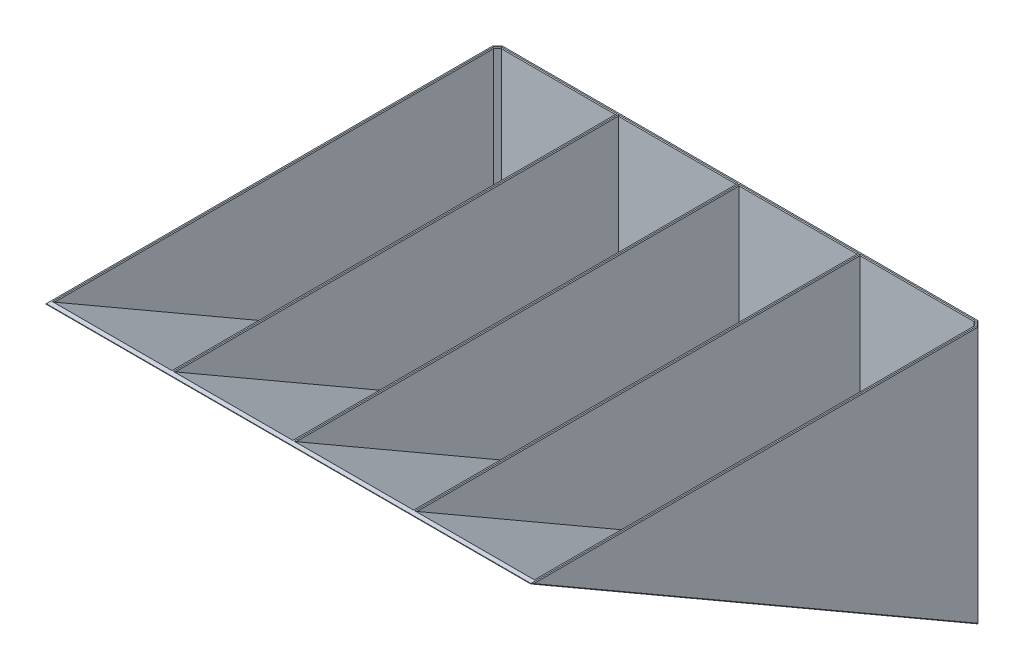
SolidWorks part; units mm, degrees
ref_plane "Front" through (0, 0, 0) normal (0, 0, 1) x (1, 0, 0)
ref_plane "Top" through (0, 0, 0) normal (0, 1, 0) x (1, 0, 0)
ref_plane "Right" through (0, 0, 0) normal (1, 0, 0) x (0, 0, -1)
sketch "Sketch1" plane through (0, 0, 0) normal (1, 0, 0) x (0, 0, -1)
  line L0 (0, 139.892) -> (0, 0)
  line L1 (0, 0) -> (-242.3, 139.892)
  line L2 (-242.3, 139.892) -> (0, 139.892)
  dimension "D1" = 60
extrude "Boss-Extrude1" add sketch "Sketch1" along normal up to surface (130.1 mm away) and the other way up to surface (130.1 mm away)
chamfer "Back Corner Chams" distance 3 angle 45 2 edges at (130.1, 69.946, 0) (-130.1, 69.946, 0)
shell "Compartment" thickness 1.5
sketch "Sketch7" plane through (0, 0, 0) normal (1, 0, 0) x (0, 0, -1)
  line L0 (-233.5531, 134.842) -> (-229.0426, 129.4665)
  line L1 (0, 0) -> (-242.3, 139.892) construction
  line L2 (-229.0426, 129.4665) -> (-226.5135, 128.0063)
  line L3 (-226.5135, 128.0063) -> (-224.1135, 129.392)
  line L4 (-233.5531, 134.842) -> (-224.1135, 129.392)
  dimension "D1" = 60
  dimension "D2" = 2.4
  dimension "D3" = 10.1
  dimension "D4" = 20
  dimension "D5" = 10.9
extrude "Stacker Rib" add sketch "Sketch7" along normal offset from surface 10.1 and the other way offset from surface (120 mm away) 10.1 up to face at (130.1, 93.8387, 82.7667) other way up to face at (-130.1, 93.8387, 82.7667)
chamfer "Stacker Rib Cham" distance 2.4 angle 45 2 edges at (120, 128.7364, 227.778) (-120, 128.7364, 227.778)
pattern_linear "LPattern1" count 8 spacing 35 along (0, -0.5, -0.866) of "Stacker Rib", "Stacker Rib Cham"
sketch "Sketch3" plane through (0, 0, 0) normal (1, 0, 0) x (0, 0, -1)
  line L3 (0, 0) -> (0, 139.892)
  line L4 (-242.3, 139.892) -> (0, 0)
  line L5 (0, 139.892) -> (-242.3, 139.892)
  line L6 (0, 0) -> (0, 139.892)
  line L7 (-242.3, 139.892) -> (0, 0)
  line L8 (0, 139.892) -> (-242.3, 139.892)
  dimension "D1" = 0
extrude "Center Divider" add sketch "Sketch3" along normal mid plane 1.5
sketch "Sketch4" [suppressed] plane through (0, 139.892, 0) normal (0, 1, 0) x (1, 0, 0)
  line L0 (-128.6, -121.4607) -> (-42.8667, -121.4607) construction
  line L1 (-128.6, -239.3) -> (-128.6, -3.6213) construction
  line L2 (-42.8667, -121.4607) -> (42.8667, -121.4607) construction
  line L3 (42.8667, -121.4607) -> (128.6, -121.4607) construction
  line L4 (128.6, -3.6213) -> (128.6, -239.3) construction
ref_plane "3 Compartment Divider Plane" [suppressed] through (-42.8667, 0, 0) normal (1, 0, 0) x (0, 0, -1)
sketch "Sketch5" [suppressed] plane through (-42.8667, 0, 0) normal (1, 0, 0) x (0, 0, -1)
  line L3 (0, 0) -> (0, 139.892)
  line L4 (0, 139.892) -> (-242.3, 139.892)
  line L5 (-242.3, 139.892) -> (0, 0)
  line L6 (0, 0) -> (0, 139.892)
  line L7 (0, 139.892) -> (-242.3, 139.892)
  line L8 (-242.3, 139.892) -> (0, 0)
  dimension "D1" = 0
extrude "3 Divider Left" [suppressed] add sketch "Sketch5" along normal mid plane 1.5
mirror "3 Divider Right" [suppressed] about plane through (0, 0, 0) normal (1, 0, 0)
ref_plane "4 Compartment Divider Plane" through (-64.675, 0, 0) normal (1, 0, 0) x (0, 0, -1)
sketch "Sketch6" plane through (-64.675, 0, 0) normal (1, 0, 0) x (0, 0, -1)
  line L3 (0, 0) -> (0, 139.892)
  line L4 (-242.3, 139.892) -> (0, 0)
  line L5 (0, 139.892) -> (-242.3, 139.892)
  line L6 (0, 0) -> (0, 139.892)
  line L7 (-242.3, 139.892) -> (0, 0)
  line L8 (0, 139.892) -> (-242.3, 139.892)
  dimension "D1" = 0
extrude "4 Compartment Left Divider" add sketch "Sketch6" along normal mid plane 1.5
mirror "4 Compartment Right Divider" about plane through (0, 0, 0) normal (1, 0, 0) of "4 Compartment Left Divider"
chamfer "Body Deburs" distance 0.4 angle 45 16 edges at (95.9518, 139.892, 1.5) (127.5393, 139.892, 2.5607) (128.6, 139.892, 121.4607) (-127.5393, 139.892, 2.5607) (-128.6, 139.892, 121.4607) (0, 139.892, 242.3) (128.6, 0.866, 1.5) (-128.6, 0.866, 1.5) (0, 0, 0) (130.1, 70.812, 122.65) (130.1, 139.892, 122.65) (128.6, 139.892, 1.5) (0, 139.892, 0) (-128.6, 139.892, 1.5) (-130.1, 139.892, 122.65) (-130.1, 70.812, 122.65)
chamfer "2 Compartment Deburs" [suppressed] distance 0.4 angle 45
chamfer "3 Compartment Deburs" [suppressed] distance 0.4 angle 45
chamfer "4 Compartment Deburs" distance 0.4 angle 45 9 edges at (65.425, 139.892, 120.2) (63.925, 139.892, 120.4) (32.3375, 139.892, 1.5) (0.75, 139.892, 120.4) (-0.75, 139.892, 120.4) (-63.925, 139.892, 120.4) (-32.3375, 139.892, 1.5) (-65.425, 139.892, 120.4) (-96.2347, 139.892, 1.5)
